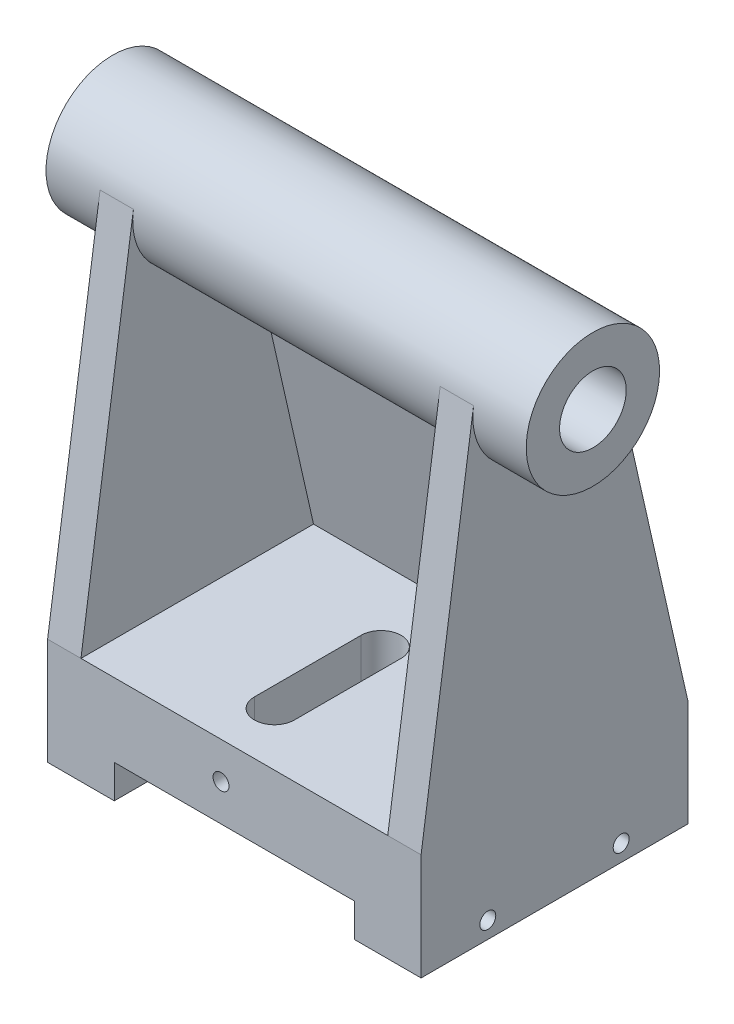
SolidWorks part; units mm, degrees
ref_plane "Front Plane" through (0, 0, 0) normal (0, 0, 1) x (1, 0, 0)
ref_plane "Top Plane" through (0, 0, 0) normal (0, 1, 0) x (1, 0, 0)
ref_plane "Right Plane" through (0, 0, 0) normal (1, 0, 0) x (0, 0, -1)
sketch "Sketch1" plane through (0, 0, 0) normal (0, 1, 0) x (1, 0, 0)
  line L1 (44.45, -31.75) -> (-44.45, -31.75)
  line L2 (44.45, -31.75) -> (44.45, 31.75)
  line L3 (44.45, 31.75) -> (-44.45, 31.75)
  line L4 (-44.45, -31.75) -> (-44.45, 31.75)
  line L5 (44.45, -31.75) -> (-44.45, 31.75) construction
  line L6 (44.45, 31.75) -> (-44.45, -31.75) construction
  point P0 (0, 0)
  dimension "D1" = 88.9
  dimension "D2" = 63.5
extrude "Boss-Extrude1" add sketch "Sketch1" along normal mid plane 25.4
sketch "Sketch2" plane through (0, 0, 31.75) normal (0, 0, 1) x (1, 0, 0)
  line L0 (0, -8.7312) -> (0, 0) construction
  line L1 (28.575, -12.7) -> (-28.575, -12.7)
  line L2 (28.575, -12.7) -> (28.575, -4.7625)
  line L3 (28.575, -4.7625) -> (-28.575, -4.7625)
  line L4 (-28.575, -12.7) -> (-28.575, -4.7625)
  line L5 (28.575, -12.7) -> (-28.575, -4.7625) construction
  line L6 (28.575, -4.7625) -> (-28.575, -12.7) construction
  line L7 (-44.45, -12.7) -> (44.45, -12.7) construction
  point P0 (0, -8.7312)
  dimension "D1" = 7.9375
  dimension "D2" = 57.15
extrude "Cut-Extrude1" cut sketch "Sketch2" against normal through all
hole_wizard "#10-24 Tapped Hole1" positions "Sketch3" profile "Sketch4" tap size "#10-24" standard "ANSI Inch" end condition through all
sketch "Sketch3" plane through (0, 0, 31.75) normal (0, 0, 1) x (1, 0, 0)
  line L2 (-44.45, 12.7) -> (44.45, 12.7) construction
  point P0 (-3.175, 3.9688)
  point P11 (-6.4115, 3.9688)
  dimension "D1" = 8.7312
  dimension "D2" = 3.175
sketch "Sketch4" plane through (-3.175, 3.9688, 31.75) normal (1, 0, 0) x (0, -1, 0)
  line L0 (0, 0) -> (0, 63.5)
  line L1 (0, 63.5) -> (1.8986, 63.5)
  line L2 (1.8986, 63.5) -> (1.8986, 0)
  line L5 (1.8986, 0) -> (0, 0)
  line L11 (0, -6.35) -> (0, 107.95) construction
  dimension "Thru Tap Drill Dia." = 3.7973
  dimension "Thru Tap Drill Depth" = 63.5
cosmetic thread "Hole Thread1" parameters "D2"=4.826
sketch "Sketch5" plane through (0, 12.7, 0) normal (0, 1, 0) x (1, 0, 0)
  line L0 (-3.175, -19.05) -> (-3.175, 6.35) construction
  line L1 (-7.9375, -19.05) -> (-7.9375, 6.35)
  line L2 (1.5875, -19.05) -> (1.5875, 6.35)
  line L3 (-44.45, -31.75) -> (44.45, -31.75) construction
  arc A0 (-7.9375, -19.05) -> (1.5875, -19.05) centre (-3.175, -19.05) ccw
  arc A1 (1.5875, 6.35) -> (-7.9375, 6.35) centre (-3.175, 6.35) ccw
  point P3 (-3.175, -6.35)
  point P8 (-7.9375, -6.35)
  dimension "D1" = 4.7625
  dimension "D2" = 9.525
  dimension "D3" = 25.4
  dimension "D4" = 12.7
  dimension "D5" = 3.175
extrude "Cut-Extrude2" cut sketch "Sketch5" against normal blind 25.4
sketch "Sketch6" plane through (0, 0, 0) normal (1, 0, 0) x (0, 0, -1)
  line L0 (-31.75, 12.7) -> (-19.2677, 99.0453)
  line L1 (-31.75, -12.7) -> (31.75, -12.7) construction
  line L2 (11.9273, 100.2785) -> (31.75, 12.7)
  line L3 (-3.556, 96.774) -> (-3.556, 23.5267) construction
  line L4 (-31.75, 12.7) -> (-31.75, -12.7) construction
  line L7 (-31.75, 12.7) -> (31.75, 12.7)
  arc A0 (-19.2677, 99.0453) -> (11.9273, 100.2785) centre (-3.556, 96.774) ccw
  dimension "D3" = 31.75
  dimension "D1" = 28.194
  dimension "D2" = 109.474
extrude "Boss-Extrude2" add sketch "Sketch6" against normal blind 7.9375 from surface starting at face at (44.45, 0, 0)
extrude "Boss-Extrude3" add sketch "Sketch6<2>" along normal blind 7.9375 from surface starting at face at (-44.45, 0, 0)
sketch "Sketch6<2>" plane through (0, 0, 0) normal (1, 0, 0) x (0, 0, -1) same geometry as "Sketch6"
ref_plane "Plane1" through (0, 7.455, -32.9372) normal (0, 0.2208, -0.9753) x (-1, 0, 0)
sketch "Sketch7" plane through (0, 7.455, -32.9372) normal (0, 0.2208, -0.9753) x (-1, 0, 0)
  line L1 (36.5125, 5.3776) -> (-36.5125, 5.3776)
  line L2 (36.5125, 5.3776) -> (36.5125, 95.1715)
  line L3 (36.5125, 95.1715) -> (-36.5125, 95.1715)
  line L4 (-36.5125, 5.3776) -> (-36.5125, 95.1715)
extrude "Boss-Extrude4" add sketch "Sketch7" against normal blind 7.9375
sketch "Sketch8" plane through (0, 0, 0) normal (1, 0, 0) x (0, 0, -1)
  circle A0 centre (-3.556, 96.774) radius 15.875
  circle A1 centre (-3.556, 96.774) radius 7.9375
  dimension "D1" = 31.75
  dimension "D2" = 15.875
extrude "Boss-Extrude5" add sketch "Sketch8" along normal mid plane 114.3
hole_wizard "#10-24 Tapped Hole2" positions "Sketch9" profile "Sketch10" tap size "#10-24" standard "ANSI Inch" end condition up to next
sketch "Sketch9" plane through (44.45, 0, 0) normal (1, 0, 0) x (0, 0, -1)
  line L0 (-31.75, 12.7) -> (-31.75, -12.7) construction
  line L1 (31.75, 12.7) -> (31.75, -12.7) construction
  line L2 (-31.75, -12.7) -> (31.75, -12.7) construction
  point P0 (-15.875, -8.7312)
  point P2 (15.875, -8.7312)
  dimension "D1" = 15.875
  dimension "D2" = 15.875
  dimension "D3" = 3.9688
  dimension "D4" = 3.9688
sketch "Sketch10" plane through (44.45, -8.7312, 15.875) normal (0, 1, 0) x (0, 0, -1)
  line L0 (0, 0) -> (0, 15.875)
  line L1 (0, 15.875) -> (1.8986, 15.875)
  line L2 (1.8986, 15.875) -> (1.8986, 0)
  line L5 (1.8986, 0) -> (0, 0)
  line L11 (0, -6.35) -> (0, 107.95) construction
  dimension "Thru Tap Drill Dia." = 3.7973
  dimension "Thru Tap Drill Depth" = 15.875
cosmetic thread "Hole Thread2" parameters "D2"=4.826
cosmetic thread "Hole Thread3" parameters "D2"=4.826
ref_plane "Plane2" through (44.45, -12.7, 31.75) normal (0, -1, 0) x (-1, 0, 0)
